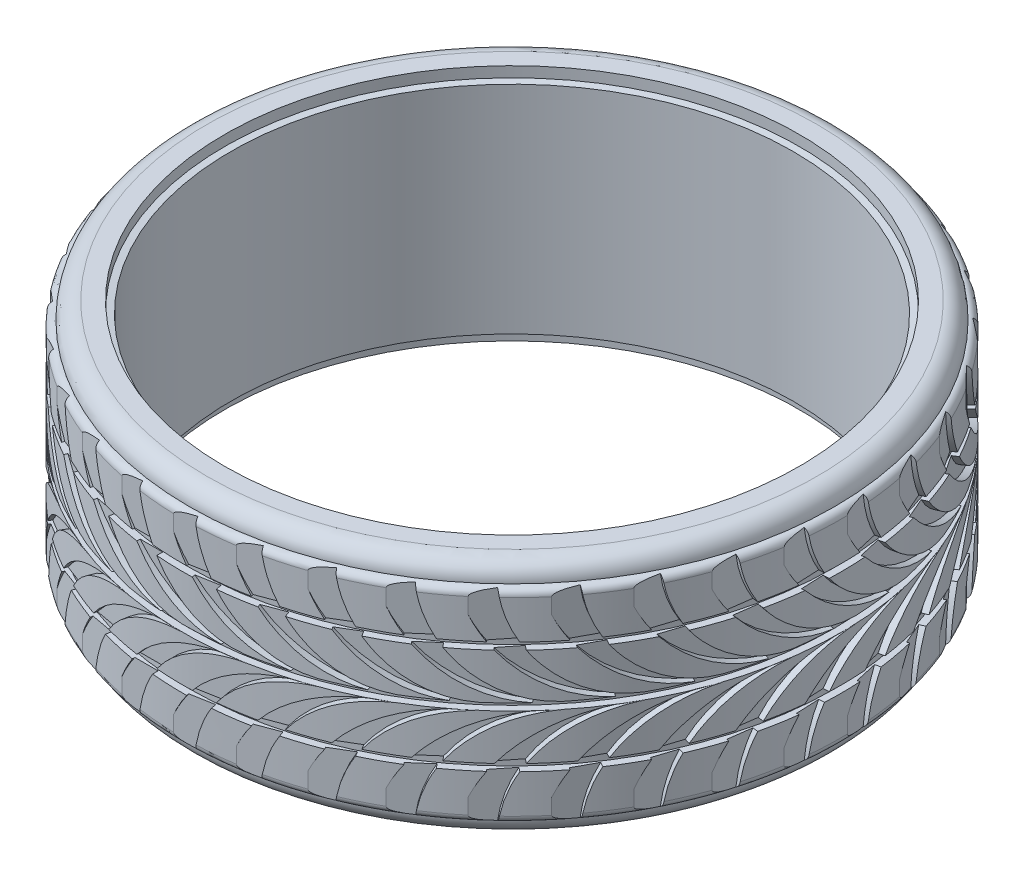
SolidWorks part; units mm, degrees
material "BUTYL"
ref_plane "Plano frontal" through (0, 0, 0) normal (0, 0, 1) x (1, 0, 0)
ref_plane "Plano superior" through (0, 0, 0) normal (0, 1, 0) x (1, 0, 0)
ref_plane "Plano direito" through (0, 0, 0) normal (1, 0, 0) x (0, 0, -1)
sketch "Esboço1" plane through (0, 0, 0) normal (0, 0, 1) x (1, 0, 0)
  line L0 (-40.1, -8.5) -> (-41, -8.5)
  line L1 (-41, -8.5) -> (-40.1, -8.5)
  line L2 (-40.1, -8.5) -> (-40.1149, -8.5231)
  line L3 (-47.912, 7) -> (-20.9277, 7) construction
  line L5 (-40.1, 22.351) -> (-40.1, -8.5)
  line L6 (0, -15.9975) -> (-41, -8.5) construction
  line L7 (-41, 22.5) -> (-40.1, 22.351)
  line L8 (-41, 24) -> (-41, 22.5)
  line L9 (-41, -8.5) -> (-41, -10)
  line L10 (-41, -10) -> (-43.5, -10)
  line L11 (-46, -7.5) -> (-46, 21.5)
  line L12 (-43.5, 24) -> (-41, 24)
  line L13 (0, 15.3512) -> (0, -15.3512) construction
  arc A0 (-43.5, -10) -> (-46, -7.5) centre (-43.5, -7.5) cw
  arc A1 (-46, 21.5) -> (-43.5, 24) centre (-43.5, 21.5) cw
  point P15 (-46, -10)
  point P18 (-46, 24)
  dimension "D2" = 2.5
  dimension "D3" = 17
  dimension "D4" = 5
  dimension "D5" = 1.5
  dimension "D6" = 17
  dimension "D7" = 40.1
  dimension "D8" = 1.5
  dimension "D12" = 15.5
  dimension "D13" = 0.9
  dimension "D14" = 0.9
  dimension "D15" = 10
revolve "Revolução1" add sketch "Esboço1" angle 360 about L13 region at (-43.0526, 6.9947, 0)
sketch "Esboço2" plane through (0, 0, 0) normal (1, 0, 0) x (0, 0, -1)
  line L0 (46, 7) -> (0, 7) construction
  line L1 (-46, 21.5) -> (-47, 21.5)
  line L2 (-46, 21.5) -> (-46, 15)
  line L3 (-46, 15) -> (-47, 15)
  line L4 (-47, 21.5) -> (-47, 15)
  line L5 (-46, 14) -> (-47, 14)
  line L6 (-46, 14) -> (-46, 7.5)
  line L7 (-46, 7.5) -> (-47, 7.5)
  line L8 (-47, 14) -> (-47, 7.5)
  line L9 (-46, -7.5) -> (-47, -7.5)
  line L10 (-46, -7.5) -> (-46, -1)
  line L11 (-46, -1) -> (-47, -1)
  line L12 (-47, -7.5) -> (-47, -1)
  line L13 (-46, 0) -> (-47, 0)
  line L14 (-46, 0) -> (-46, 6.5)
  line L15 (-46, 6.5) -> (-47, 6.5)
  line L16 (-47, 0) -> (-47, 6.5)
  line L17 (0, 0) -> (0, 8.6175) construction
  line L18 (-46, 21.5) -> (-46, -7.5) construction
  line L19 (-46, 21.5) -> (-46, -7.5) construction
  line L20 (46, -7.5) -> (46, 21.5) construction
  line L21 (-46, 7) -> (-36.181, 7) construction
  dimension "D1" = 1
  dimension "D2" = 6.5
  dimension "D3" = 0
  dimension "D4" = 0.5
  dimension "D5" = 0.5
  dimension "D6" = 1
  dimension "D7" = 1
revolve "Revolução2" add sketch "Esboço2" angle 360 about L17
ref_plane "Plano3" through (0, 0, 46) normal (0, 0, 1) x (1, 0, 0)
fillet "Filete22" radius 1 2 edges at (0, 21.5, -47) (0, -7.5, -47)
sketch "Esboço8" plane through (0, 0, 46) normal (0, 0, 1) x (1, 0, 0)
  line L0 (5.2839, 7.4956) -> (8.3735, 7.4956)
  line L1 (5.2839, 6.4956) -> (5.2839, 7.4956) construction
  line L2 (-0.9153, 6.9956) -> (13.3184, 6.9956) construction
  line L3 (-11.0521, 23.7956) -> (-6.7161, 23.7956)
  line L4 (-11.0521, -9.8044) -> (-6.7161, -9.8044)
  line L5 (5.2839, 6.4956) -> (8.3735, 6.4956)
  arc A0 (-11.0521, 23.7956) -> (5.2839, 7.4956) centre (6.8732, 25.4243) ccw
  arc A1 (8.3735, 7.4956) -> (-6.7161, 23.7956) centre (8.8387, 23.0607) cw
  arc A2 (8.3735, 6.4956) -> (-6.7161, -9.8044) centre (8.8387, -9.0696) ccw
  arc A3 (-11.0521, -9.8044) -> (5.2839, 6.4956) centre (6.8732, -11.4332) cw
  dimension "D1" = 12
  dimension "D2" = 16.3
extrude "Corte-extrusão3" cut sketch "Esboço8" along normal through all
pattern_circular "PadrãoCircular1" count 35 over 360 about axis through (0, -8.5, 0) along (0, 1, 0) of "Corte-extrusão3"
